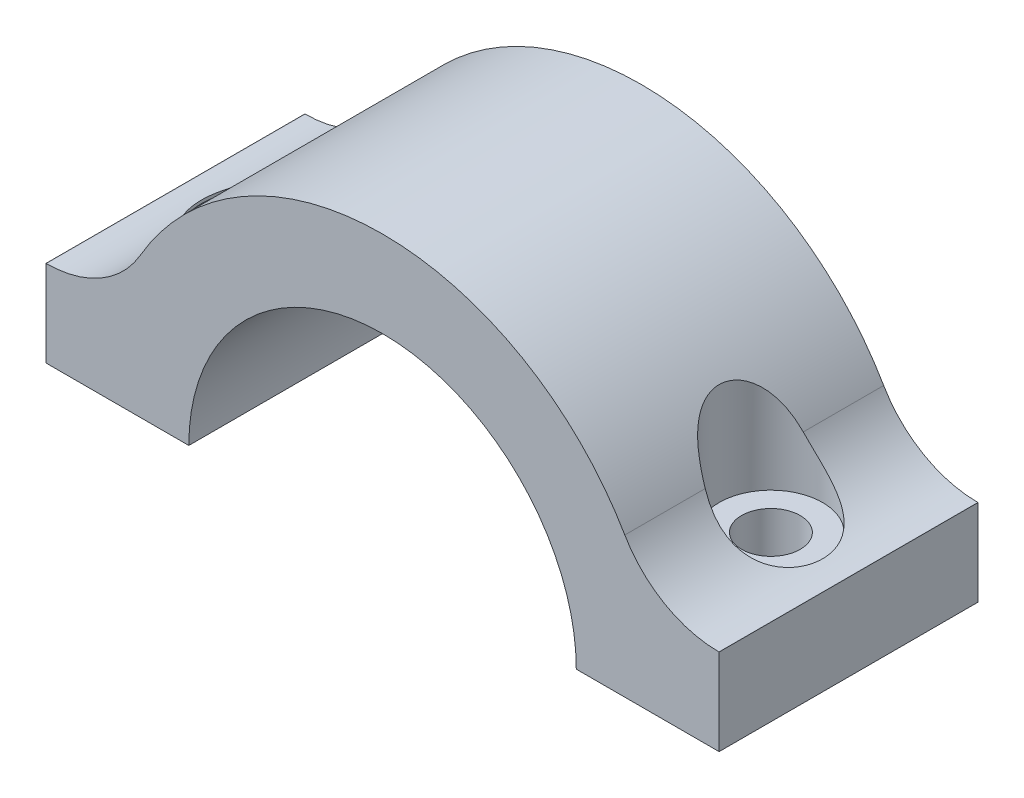
SolidWorks part; units mm, degrees
ref_plane "Ön Düzlem" through (0, 0, 0) normal (0, 0, 1) x (1, 0, 0)
ref_plane "Üst Düzlem" through (0, 0, 0) normal (0, 1, 0) x (1, 0, 0)
ref_plane "Sağ Düzlem" through (0, 0, 0) normal (1, 0, 0) x (0, 0, -1)
sketch "Çizim1" plane through (0, 0, 0) normal (0, 0, 1) x (1, 0, 0)
  line L0 (-11.225, 0) -> (-19.5, 0)
  line L1 (11.225, 0) -> (19.5, 0)
  line L2 (-19.5, 0) -> (-19.5, 5)
  line L3 (-19.5, 5) -> (-15.4354, 5)
  line L5 (0, 0) -> (0, 11.225) construction
  line L7 (19.5, 5) -> (15.4354, 5)
  line L8 (19.5, 0) -> (19.5, 5)
  circle A0 centre (0, 0) radius 11.225
  arc A1 (15.4354, 5) -> (-15.4354, 5) centre (0, 0) ccw
  circle A2 centre (0, 0) radius 16.225 construction
  point P8 (15.3833, 5.1579)
  dimension "D1" = 22.45
  dimension "D3" = 39
  dimension "D4" = 5
  dimension "D2" = 5
extrude "Yükseklik-Ekstrüzyon1" add sketch "Çizim1" along normal blind 15 contours L7 A1 L3 L2 L0 A0 L1 L8 region at (-15.3625, 0.4224, 0)
sketch "Çizim2" plane through (0, 0, 0) normal (0, -1, 0) x (1, 0, 0)
  line L0 (-19.5, 7.5) -> (19.5, 7.5) construction
  line L1 (-19.5, 15) -> (-19.5, 0) construction
  line L2 (19.5, 15) -> (19.5, 0) construction
  circle A0 centre (-15, 7.5) radius 1.7
  circle A1 centre (15, 7.5) radius 1.7
  dimension "D1" = 3.4
  dimension "D2" = 3.4
  dimension "D3" = 4.5
  dimension "D4" = 4.5
extrude "Kes-Ekstrüzyon2" cut sketch "Çizim2" against normal blind 15
fillet "Radyus3" radius 6.3 2 edges at (-15.4354, 5, 12.0717) (15.4354, 5, 12.0717)
sketch "Çizim3" plane through (0, 5, 0) normal (0, 1, 0) x (1, 0, 0)
  circle A0 centre (-15, -7.5) radius 3
  circle A1 centre (15, -7.5) radius 3
  dimension "D1" = 6
  dimension "D2" = 6
extrude "Kes-Ekstrüzyon3" cut sketch "Çizim3" along normal blind 15
